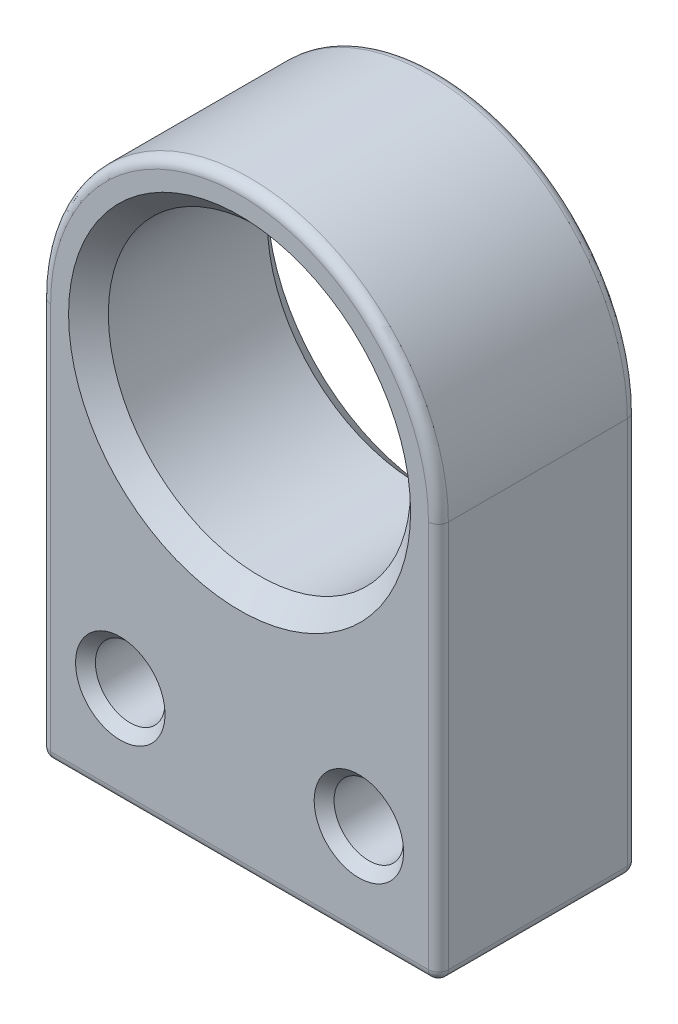
SolidWorks part; units mm, degrees
ref_plane "前视基准面" through (0, 0, 0) normal (0, 0, 1) x (1, 0, 0)
ref_plane "上视基准面" through (0, 0, 0) normal (0, 1, 0) x (1, 0, 0)
ref_plane "右视基准面" through (0, 0, 0) normal (1, 0, 0) x (0, 0, -1)
sketch "草图1" plane through (0, 0, 0) normal (0, 0, 1) x (1, 0, 0)
  line L0 (-6, 0) -> (6, 0) construction
  line L1 (-10, -5) -> (10, -5)
  line L2 (-10, -5) -> (-10, 5)
  line L3 (-10, 5) -> (10, 5)
  line L4 (10, -5) -> (10, 5)
  line L5 (-10, -5) -> (10, 5) construction
  line L6 (-10, 5) -> (10, -5) construction
  circle A0 centre (-6, 0) radius 1.75
  circle A1 centre (6, 0) radius 1.75
  point P0 (0, 0)
  point P9 (0, 0)
  dimension "D4" = 3.5
  dimension "D1" = 20
  dimension "D2" = 10
  dimension "D3" = 12
extrude "凸台-拉伸1" add sketch "草图1" along normal blind 10
sketch "草图2" plane through (0, 0, 10) normal (0, 0, 1) x (1, 0, 0)
  line L0 (10, 5) -> (-10, 5) construction
  line L1 (-10, 5) -> (10, 5)
  line L2 (10, 5) -> (10, 15)
  line L3 (-10, 5) -> (-10, 15)
  circle A0 centre (0, 15) radius 10
  circle A1 centre (0, 15) radius 7.6
  line M3 (10, 5) -> (-10, 5)
  dimension "D1" = 20
  dimension "D2" = 15.2
extrude "凸台-拉伸2" add sketch "草图2" against normal blind 10 contours A0 L3 L1 | A0 | A0 L2 M3 region at (-7.7663, 7.2337, 10) region at (7.7663, 7.2337, 10) region at (-6.8711, 8.1289, 10)
chamfer "倒角1" distance 1 angle 45 2 edges at (7.6, 15, 10) (7.6, 15, 0)
chamfer "倒角2" distance 0.5 angle 45 4 edges at (7.75, 0, 0) (7.75, 0, 10) (-4.25, 0, 0) (-4.25, 0, 10)
fillet "圆角1" radius 0.5 10 edges at (10, 5, 10) (0, 25, 10) (10, 5, 0) (0, 25, 0) (0, -5, 10) (10, -5, 5) (0, -5, 0) (-10, 5, 10) (-10, -5, 5) (-10, 5, 0)
